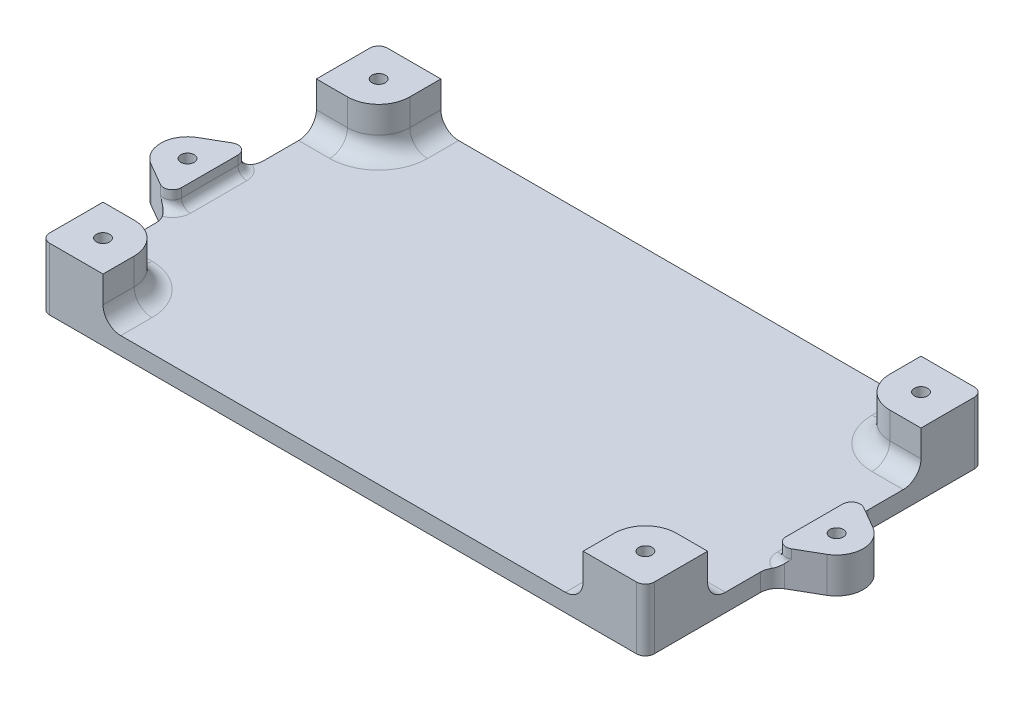
SolidWorks part; units mm, degrees
ref_plane "Front Plane" through (0, 0, 0) normal (0, 0, 1) x (1, 0, 0)
ref_plane "Top Plane" through (0, 0, 0) normal (0, 1, 0) x (1, 0, 0)
ref_plane "Right Plane" through (0, 0, 0) normal (1, 0, 0) x (0, 0, -1)
sketch "Sketch1" plane through (0, 0, 0) normal (0, 1, 0) x (1, 0, 0)
  line L1 (-34, 19) -> (34, 19)
  line L2 (-34, 19) -> (-34, -19)
  line L3 (-34, -19) -> (34, -19)
  line L4 (34, 19) -> (34, -19)
  line L5 (0, -19) -> (0, 19) construction
  line L6 (-34, 0) -> (34, 0) construction
  point P4 (0, 0)
  point P5 (34, -15.8404)
  point P132 (0, 0)
  dimension "D1" = 68
  dimension "D2" = 38
extrude "Boss-Extrude1" add sketch "Sketch1" along normal blind 2
sketch "Sketch2" plane through (0, 2, 0) normal (0, 1, 0) x (1, 0, 0)
  line L0 (34, 19) -> (-34, 19) construction
  line L1 (-30.5, 15.5) -> (30.5, 15.5) construction
  line L2 (-30.5, 15.5) -> (-30.5, -15.5) construction
  line L3 (-30.5, -15.5) -> (30.5, -15.5) construction
  line L4 (30.5, 15.5) -> (30.5, -15.5) construction
  line L5 (0, -15.5) -> (0, 15.5) construction
  line L6 (-30.5, 0) -> (30.5, 0) construction
  line L7 (-27, -15.5) -> (-27, -19)
  line L8 (-34, -19) -> (34, -19) construction
  line L9 (-27, -19) -> (-34, -19)
  line L10 (-34, -19) -> (-34, -12)
  line L11 (-34, 19) -> (-34, -19) construction
  line L12 (-34, -12) -> (-30.5, -12)
  circle A0 centre (-30.5, 15.5) radius 3.5 construction
  circle A1 centre (30.5, 15.5) radius 3.5 construction
  circle A2 centre (30.5, -15.5) radius 3.5 construction
  arc A3 (-27, -15.5) -> (-30.5, -12) centre (-30.5, -15.5) ccw
  point P152 (0, 0)
  dimension "D2" = 31
  dimension "D3" = 61
extrude "Boss-Extrude2" add sketch "Sketch2" along normal blind 5
sketch "Sketch3" plane through (0, 7, 0) normal (0, 1, 0) x (1, 0, 0)
  circle A0 centre (-30.5, -15.5) radius 0.75
  arc A1 (-27, -15.5) -> (-30.5, -12) centre (-30.5, -15.5) ccw construction
  dimension "D1" = 1.5
ref_plane "Plane1" through (0, 1, 0) normal (0, -1, 0) x (-1, 0, 0)
extrude "Cut-Extrude1" cut sketch "Sketch3" against normal up to surface (6 mm away)
mirror "Mirror1" about plane through (0, 0, 0) normal (0, 0, 1) of "Boss-Extrude2", "Cut-Extrude1" second plane through (0, 0, 0) second plane normal (1, 0, 0)
fillet "Fillet1" radius 2 12 edges at (-28.0251, 2, 13.0251) (-32.25, 2, 12) (-27, 2, 17.25) (28.0251, 2, 13.0251) (32.25, 2, 12) (27, 2, 17.25) (-28.0251, 2, -13.0251) (-32.25, 2, -12) (-27, 2, -17.25) (28.0251, 2, -13.0251) (32.25, 2, -12) (27, 2, -17.25)
fillet "Fillet2" radius 1 4 edges at (34, 3.5, -19) (34, 3.5, 19) (-34, 3.5, -19) (-34, 3.5, 19)
sketch "Sketch4" plane through (0, 0, 0) normal (0, -1, 0) x (1, 0, 0)
  line L0 (-36.5, 0) -> (36.5, 0) construction
  line L1 (-38, 2.5981) -> (-34, 4.9075)
  line L2 (-34, -18) -> (-34, 18) construction
  line L3 (-34, 4.9075) -> (-34, -4.9075)
  line L4 (-34, -4.9075) -> (-38, -2.5981)
  circle A0 centre (-36.5, 0) radius 0.75
  arc A2 (-38, -2.5981) -> (-38, 2.5981) centre (-36.5, 0) cw
  point P10 (-43.7306, -5.0512)
  point P12 (-34, -8.8362)
  point P13 (-39.0032, 0)
  dimension "D1" = 1.5
  dimension "D3" = 3
  dimension "D2" = 30
  dimension "D4" = 2.5
extrude "Boss-Extrude3" add sketch "Sketch4" against normal blind 4
mirror "Mirror7" about plane through (0, 0, 0) normal (1, 0, 0) of "Boss-Extrude3"
fillet "Fillet4" radius 2 4 edges at (-34, 1, 4.9075) (-34, 1, -4.9075) (34, 1, -4.9075) (34, 1, 4.9075)
fillet "Fillet6" radius 1 1 edges at (-34, 3, -4.9075)
fillet "Fillet7" radius 1 1 edges at (-34, 3, 4.9075)
fillet "Fillet8" radius 1 3 edges at (-34.5, 2, -4.0415) (-34, 2, 0) (-34.5, 2, 4.0415)
fillet "Fillet10" radius 1 1 edges at (34, 3, -4.9075)
fillet "Fillet11" radius 1 1 edges at (34, 3, 4.9075)
fillet "Fillet12" radius 1 3 edges at (34.5, 2, -4.0415) (34, 2, 0) (34.5, 2, 4.0415)
